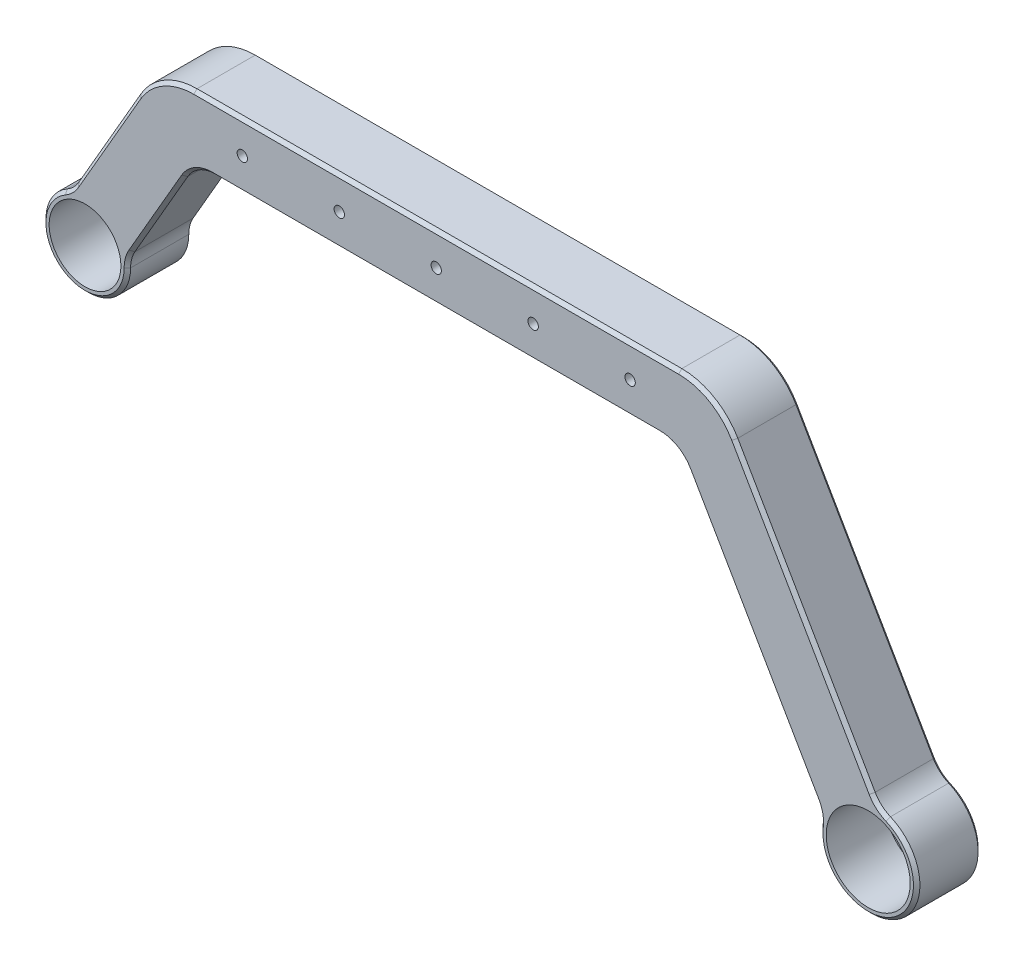
SolidWorks part; units mm, degrees
ref_plane "Front Plane" through (0, 0, 0) normal (0, 0, 1) x (1, 0, 0)
ref_plane "Top Plane" through (0, 0, 0) normal (0, 1, 0) x (1, 0, 0)
ref_plane "Right Plane" through (0, 0, 0) normal (1, 0, 0) x (0, 0, -1)
ref_axis "X" through (-88.99, 0, 0) along (1, 0, 0)
ref_axis "Y" through (0, 55, 0) along (0, -1, 0)
ref_axis "Z" through (0, 0, -88.99) along (0, 0, 1)
sketch "Sketch1" plane through (0, 0, 0) normal (0, 0, 1) x (1, 0, 0)
  line L0 (-75, -10) -> (75, -10)
  line L1 (-75, 10) -> (75, 10)
  line L3 (125, -96.6025) -> (75, -10)
  line L4 (-75, -10) -> (-100, -53.3013)
  line L5 (-117.3205, -43.3013) -> (-92.3205, 0)
  line L6 (92.3205, 0) -> (142.3205, -86.6025)
  line L7 (0, 10) -> (0, -10) construction
  line L8 (0, 0) -> (-30, 0) construction
  line L9 (0, 0) -> (30, 0) construction
  line L10 (30, 0) -> (60, 0) construction
  line L11 (-30, 0) -> (-60, 0) construction
  arc A0 (142.3205, -86.6025) -> (125, -96.6025) centre (133.6603, -91.6025) cw
  arc A1 (-100, -53.3013) -> (-117.3205, -43.3013) centre (-108.6603, -48.3013) cw
  arc A2 (-92.3205, 0) -> (-75, 10) centre (-75, -10) cw
  arc A3 (75, 10) -> (92.3205, 0) centre (75, -10) cw
  circle A4 centre (0, 0) radius 1.6
  circle A5 centre (-60, 0) radius 1.6
  circle A6 centre (-30, 0) radius 1.6
  circle A7 centre (30, 0) radius 1.6
  circle A8 centre (60, 0) radius 1.6
  point P3 (0, 0)
  dimension "D1" = 150
  dimension "D7" = 3.2
  dimension "D8" = 30
  dimension "D2" = 20
  dimension "D3" = 100
  dimension "D4" = 50
  dimension "D5" = 60
  dimension "D6" = 60
extrude "Boss-Extrude1" add sketch "Sketch1" along normal mid plane 20
sketch "Sketch2" plane through (0, 0, 0) normal (0, 0, 1) x (1, 0, 0)
  line L0 (125.1603, -91.6025) -> (142.1603, -91.6025) construction
  circle A0 centre (-108.6603, -48.3013) radius 11.1
  circle A1 centre (-108.6603, -48.3013) radius 13.1
  circle A2 centre (-108.6603, -48.3013) radius 7.5
  circle A3 centre (133.6603, -91.6025) radius 13
  circle A4 centre (133.6603, -91.6025) radius 15
  circle A5 centre (133.6603, -91.6025) radius 5.5
  circle A6 centre (142.1603, -91.6025) radius 1.6
  circle A7 centre (125.1603, -91.6025) radius 1.6
  point P14 (133.6603, -91.6025)
  dimension "D1" = 22.2
  dimension "D3" = 15
  dimension "D4" = 26
  dimension "D6" = 11
  dimension "D7" = 3.2
  dimension "D8" = 17
  dimension "D2" = 2
  dimension "D5" = 2
extrude "Cut-Extrude1" cut sketch "Sketch2" against normal through all both and the other way through all contours A0 | A3
extrude "Boss-Extrude2" add sketch "Sketch2<3>" along normal up to surface (10 mm away) and the other way up to surface (10 mm away) contours A1 A0 region at (-121.3897, -48.3013, 0) up to face at (4.7306, -24.2929, 10) other way up to face at (4.7306, -24.2929, -10)
sketch "Sketch2<3>" plane through (0, 0, 0) normal (0, 0, 1) x (1, 0, 0) same geometry as "Sketch2"
extrude "Boss-Extrude3" add sketch "Sketch2<4>" against normal blind 3 from surface contours A0 A2 region at (-119.4463, -48.3013, 0) starting at face at (3.7028, -26.0731, 10)
sketch "Sketch2<4>" plane through (0, 0, 0) normal (0, 0, 1) x (1, 0, 0) same geometry as "Sketch2"
extrude "Boss-Extrude4" add sketch "Sketch2<5>" along normal up to surface (10 mm away) and the other way up to surface (10 mm away) contours A4 A3 region at (119.0845, -91.6025, 0) up to face at (3.7028, -26.0731, 10) other way up to face at (3.7028, -26.0731, -10)
sketch "Sketch2<5>" plane through (0, 0, 0) normal (0, 0, 1) x (1, 0, 0) same geometry as "Sketch2"
extrude "Boss-Extrude5" add sketch "Sketch2<6>" against normal blind 2 from surface contours A3 A7 A5 A6 region at (121.0279, -91.6025, 0) starting at face at (4.9591, -28.2491, 10)
sketch "Sketch2<6>" plane through (0, 0, 0) normal (0, 0, 1) x (1, 0, 0) same geometry as "Sketch2"
fillet "Fillet1" radius 10 6 edges at (136.7303, -76.9201, 0) (-113.0894, -35.9727, 0) (-95.7689, -45.9727, 0) (119.4098, -86.9201, 0) (75, -10, 0) (-75, -10, 0)
sketch "Sketch3" plane through (0, 0, 0) normal (0, 0, 1) x (1, 0, 0)
  circle A0 centre (-60, 0) radius 3
  circle A1 centre (-30, 0) radius 3
  circle A2 centre (0, 0) radius 3
  circle A3 centre (30, 0) radius 3
  circle A4 centre (60, 0) radius 3
  dimension "D1" = 6
extrude "Cut-Extrude2" cut sketch "Sketch3" against normal blind 4 from surface starting at face at (6.0225, -34.2469, 10)
chamfer "Chamfer1" distance 1 angle 45 32 edges at (0, -10, -10) (74.2265, -11.3397, -10) (-74.2265, -11.3397, -10) (97.6934, -49.3061, -10) (-86.0536, -29.1455, -10) (118.6367, -86.6074, -10) (-95.2201, -45.7049, -10) (141.1603, -104.5929, -10) (-115.2103, -59.6462, -10) (136.8461, -76.0942, -10) (-113.1318, -35.3636, -10) (113.5705, -36.8061, -10) (-101.9308, -16.6455, -10) (85, 7.3205, -10) (-85, 7.3205, -10) (0, 10, -10) (0, -10, 10) (74.2265, -11.3397, 10) (-74.2265, -11.3397, 10) (97.6934, -49.3061, 10) (-86.0536, -29.1455, 10) (118.6367, -86.6074, 10) (-95.2201, -45.7049, 10) (141.1603, -104.5929, 10) (-115.2103, -59.6462, 10) (136.8461, -76.0942, 10) (-113.1318, -35.3636, 10) (113.5705, -36.8061, 10) (-101.9308, -16.6455, 10) (85, 7.3205, 10) (-85, 7.3205, 10) (0, 10, 10)
mirror "Mirror1" about plane through (0, 0, 0) normal (0, 0, 1) of bodies 108 106
delete or keep bodies "Body-Delete/Keep 1" type keep bodies bodies 107
